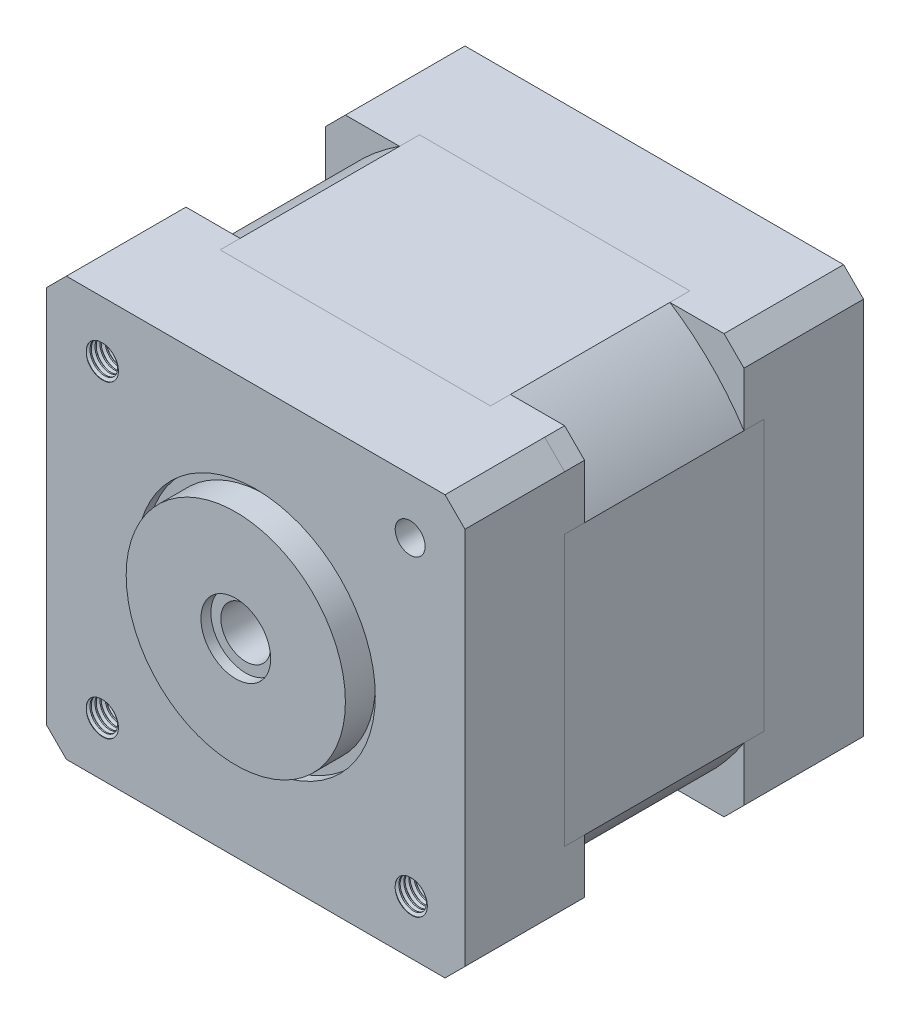
SolidWorks part; units mm, degrees
other "Cortar-Extruir6"
ref_plane "Alzado" through (0, 0, 0) normal (0, 0, 1) x (1, 0, 0)
ref_plane "Planta" through (0, 0, 0) normal (0, 1, 0) x (1, 0, 0)
ref_plane "Vista lateral" through (0, 0, 0) normal (1, 0, 0) x (0, 0, -1)
sketch "Croquis1" plane through (0, 0, 0) normal (0, 0, 1) x (1, 0, 0)
  line L1 (-21, -21) -> (21, -21)
  line L2 (-21, -21) -> (-21, 21)
  line L3 (-21, 21) -> (21, 21)
  line L4 (21, -21) -> (21, 21)
  line L5 (-21, -21) -> (21, 21) construction
  line L6 (-21, 21) -> (21, -21) construction
  point P0 (0, 0)
  dimension "D1" = 42
  dimension "D2" = 42
extrude "Saliente-Extruir2" add sketch "Croquis1" along normal blind 12
chamfer "Chaflán3" distance 2 angle 45 3 edges at (21, 21, 6) (21, -21, 6) (-21, -21, 6)
chamfer "Chaflán2" distance 2 angle 45 1 edges at (-21, 21, 6)
sketch "Croquis3" plane through (0, 0, 12) normal (0, 0, 1) x (1, 0, 0)
  line L0 (-13.5647, 21) -> (13.5647, 21)
  line L1 (19, 21) -> (-19, 21) construction
  line L2 (-21, 13.5647) -> (-21, -13.5647)
  line L3 (-21, 19) -> (-21, -19) construction
  line L4 (-13.5647, -21) -> (13.5647, -21)
  line L5 (-19, -21) -> (19, -21) construction
  line L6 (21, 13.5647) -> (21, -13.5647)
  line L7 (21, -19) -> (21, 19) construction
  arc A0 (-13.5647, 21) -> (-21, 13.5647) centre (0, 0) ccw
  arc A1 (-21, -13.5647) -> (-13.5647, -21) centre (0, 0) ccw
  arc A2 (13.5647, -21) -> (21, -13.5647) centre (0, 0) ccw
  arc A3 (21, 13.5647) -> (13.5647, 21) centre (0, 0) ccw
  dimension "D1" = 50
extrude "Cortar-Extruir1" cut sketch "Croquis3" against normal blind 2
sketch "Croquis11" plane through (0, 0, 10) normal (0, 0, 1) x (1, 0, 0)
  line L0 (-13.5647, 21) -> (13.5647, 21)
  line L1 (-13.5647, -21) -> (13.5647, -21)
  line L2 (21, 13.5647) -> (21, -13.5647)
  line L3 (-21, 13.5647) -> (-21, -13.5647)
  arc A0 (-13.5647, 21) -> (-21, 13.5647) centre (0, 0) ccw
  arc A1 (21, 13.5647) -> (13.5647, 21) centre (0, 0) ccw
  arc A2 (13.5647, -21) -> (21, -13.5647) centre (0, 0) ccw
  arc A3 (-21, -13.5647) -> (-13.5647, -21) centre (0, 0) ccw
  dimension "D1" = 50
  dimension "D2" = 21
  dimension "D3" = 21
  dimension "D4" = 21
  dimension "D5" = 21
extrude "Saliente-Extruir9" add sketch "Croquis11" along normal blind 20 separate body
ref_plane "Plano2" through (0, 0, 30) normal (0, 0, 1) x (1, 0, 0)
sketch "Croquis14" plane through (0, 0, 30) normal (0, 0, 1) x (1, 0, 0)
  line L1 (-21, -21) -> (21, -21)
  line L2 (-21, -21) -> (-21, 21)
  line L3 (-21, 21) -> (21, 21)
  line L4 (21, -21) -> (21, 21)
  line L5 (-21, -21) -> (21, 21) construction
  line L6 (-21, 21) -> (21, -21) construction
  point P0 (0, 0)
  dimension "D1" = 42
  dimension "D2" = 42
extrude "Saliente-Extruir11" add sketch "Croquis14" along normal blind 10 separate body
chamfer "Chaflán6" distance 2 angle 45 4 edges at (-21, 21, 35) (21, 21, 35) (21, -21, 35) (-21, -21, 35)
sketch "Croquis17" plane through (0, 0, 30) normal (0, 0, 1) x (1, 0, 0)
  line L0 (13.5647, 21) -> (21, 21)
  line L1 (-21, -21) -> (-13.5647, -21)
  line L2 (-21, -21) -> (-21, -13.5647)
  line L3 (-21, 21) -> (-13.5647, 21)
  line L4 (21, -21) -> (21, -13.5647)
  line L5 (-21, -21) -> (21, 21) construction
  line L6 (-21, 21) -> (21, -21) construction
  line L7 (-21, 13.5647) -> (-21, 21)
  line L8 (21, 13.5647) -> (21, 21)
  line L9 (13.5647, -21) -> (21, -21)
  arc A0 (-13.5647, 21) -> (-21, 13.5647) centre (0, 0) ccw
  arc A1 (21, 13.5647) -> (13.5647, 21) centre (0, 0) ccw
  arc A2 (-21, -13.5647) -> (-13.5647, -21) centre (0, 0) ccw
  arc A3 (13.5647, -21) -> (21, -13.5647) centre (0, 0) ccw
  dimension "D1" = 50
  dimension "D2" = 42
  dimension "D3" = 42
extrude "Saliente-Extruir12" add sketch "Croquis17" against normal blind 2
chamfer "Chaflán7" distance 2 angle 45 4 edges at (-21, -21, 29) (-21, 21, 29) (21, 21, 29) (21, -21, 29)
sketch "Croquis18" plane through (0, 0, 40) normal (0, 0, 1) x (1, 0, 0)
  circle A0 centre (0, 0) radius 12
  dimension "D1" = 24
extrude "Cortar-Extruir4" cut sketch "Croquis18" against normal blind 1
sketch "Croquis20" plane through (0, 0, 39) normal (0, 0, 1) x (1, 0, 0)
  circle A0 centre (0, 0) radius 11
  dimension "D1" = 22
extrude "Saliente-Extruir14" add sketch "Croquis20" along normal blind 3
sketch "Croquis21" plane through (0, 0, 42) normal (0, 0, 1) x (1, 0, 0)
  circle A0 centre (0, 0) radius 3.5
  dimension "D1" = 7
extrude "Cortar-Extruir5" cut sketch "Croquis21" against normal blind 1
sketch "Croquis22" plane through (0, 0, 41) normal (0, 0, 1) x (1, 0, 0)
  circle A0 centre (0, 0) radius 2.5
  dimension "D1" = 5
extrude "Cortar-Extruir6" cut sketch "Croquis22" against normal through all
chamfer "Chaflán8" distance 0.5 angle 45 1 edges at (2.5, 0, 0)
sketch "Croquis23" plane through (0, 0, 40) normal (0, 0, 1) x (1, 0, 0)
  line L0 (-33.0137, 0) -> (33.3501, 0) construction
  line L1 (0, 27.0021) -> (0, -27.9173) construction
  circle A0 centre (-15.5, 15.5) radius 1.5
  circle A1 centre (15.5, 15.5) radius 1.5
  circle A2 centre (15.5, -15.5) radius 1.5
  circle A3 centre (-15.5, -15.5) radius 1.5
  dimension "D1" = 3
  dimension "D2" = 31
  dimension "D3" = 31
  dimension "D4" = 31
  dimension "D5" = 31
extrude "Cortar-Extruir7" cut sketch "Croquis23" against normal blind 4.5
thread "Rosca1" pitch 0.5 method cut profile "Perfil de rosca2" start angle 0, offset 1, length 5, pitch 0.5, diameter 3
ref_plane "Plano4" through (-17, 15.5, 41) normal (0, -1, 0) x (-1, 0, 0)
sketch "Perfil de rosca2" plane through (-17, 15.5, 41) normal (0, -1, 0) x (-1, 0, 0)
  line L0 (0, 0) -> (0, 0.5) construction
  line L1 (0, 0) -> (0.2706, 0.1562)
  line L2 (0.2706, 0.1562) -> (0.2706, 0.2187)
  line L3 (0.2706, 0.2187) -> (0, 0.375)
  line L4 (0.2706, 0.1875) -> (0, 0.1875) construction
  line L11 (0, 0) -> (0, 0.375)
  point P2 (0, 0)
  dimension "Pitch" = 0.5
  dimension "Profile_Angle" = 60
  dimension "Profile_Land" = 0.0625
  dimension "Profile_Height" = 0.2706
thread "Rosca2" pitch 0.5 method cut profile "Perfil de rosca3" start angle 0, offset 1, length 5, pitch 0.5, diameter 3
ref_plane "Plano5" through (-17, -15.5, 41) normal (0, -1, 0) x (-1, 0, 0)
sketch "Perfil de rosca3" plane through (-17, -15.5, 41) normal (0, -1, 0) x (-1, 0, 0)
  line L0 (0, 0) -> (0, 0.5) construction
  line L1 (0, 0) -> (0.2706, 0.1562)
  line L2 (0.2706, 0.1562) -> (0.2706, 0.2187)
  line L3 (0.2706, 0.2187) -> (0, 0.375)
  line L4 (0.2706, 0.1875) -> (0, 0.1875) construction
  line L11 (0, 0) -> (0, 0.375)
  point P2 (0, 0)
  dimension "Pitch" = 0.5
  dimension "Profile_Angle" = 60
  dimension "Profile_Land" = 0.0625
  dimension "Profile_Height" = 0.2706
thread "Rosca3" pitch 0.5 method cut profile "Perfil de rosca4" start angle 0, offset 1, length 5, pitch 0.5, diameter 3
ref_plane "Plano6" through (14, -15.5, 41) normal (0, -1, 0) x (-1, 0, 0)
sketch "Perfil de rosca4" plane through (14, -15.5, 41) normal (0, -1, 0) x (-1, 0, 0)
  line L0 (0, 0) -> (0, 0.5) construction
  line L1 (0, 0) -> (0.2706, 0.1562)
  line L2 (0.2706, 0.1562) -> (0.2706, 0.2187)
  line L3 (0.2706, 0.2187) -> (0, 0.375)
  line L4 (0.2706, 0.1875) -> (0, 0.1875) construction
  line L11 (0, 0) -> (0, 0.375)
  point P2 (0, 0)
  dimension "Pitch" = 0.5
  dimension "Profile_Angle" = 60
  dimension "Profile_Land" = 0.0625
  dimension "Profile_Height" = 0.2706
